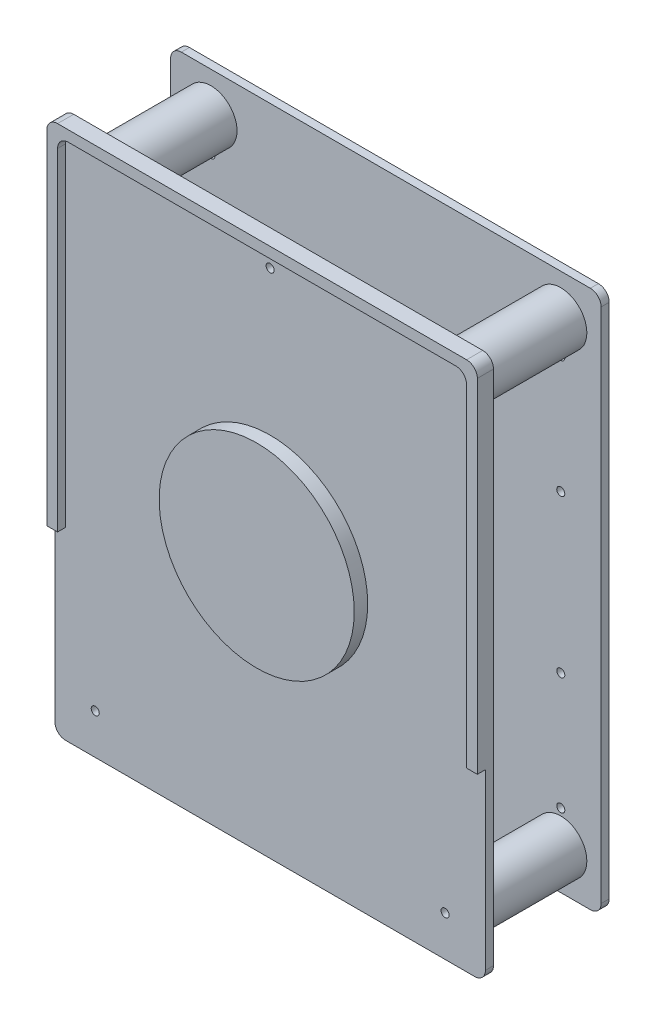
SolidWorks part; units mm, degrees
ref_plane "Front Plane" through (0, 0, 0) normal (0, 0, 1) x (1, 0, 0)
ref_plane "Top Plane" through (0, 0, 0) normal (0, 1, 0) x (1, 0, 0)
ref_plane "Right Plane" through (0, 0, 0) normal (1, 0, 0) x (0, 0, -1)
sketch "Sketch1" plane through (0, 0, 0) normal (0, 0, 1) x (1, 0, 0)
  line L0 (80, 0) -> (80, 200) construction
  line L1 (4, 0) -> (156, 0)
  line L2 (0, 4) -> (0, 196)
  line L3 (4, 200) -> (156, 200)
  line L4 (160, 4) -> (160, 196)
  line L5 (0, 100) -> (160, 100) construction
  arc A0 (4, 0) -> (0, 4) centre (4, 4) cw
  arc A1 (156, 0) -> (160, 4) centre (156, 4) ccw
  arc A2 (156, 200) -> (160, 196) centre (156, 196) cw
  arc A3 (0, 196) -> (4, 200) centre (4, 196) cw
  circle A4 centre (15, 15) radius 1.495
  circle A5 centre (145, 15) radius 1.495
  circle A6 centre (80, 190) radius 1.495
  circle A7 centre (80, 100) radius 36.25
  circle A8 centre (15, 15) radius 9.6889
  circle A9 centre (145, 15) radius 9.6889
  circle A10 centre (145, 185) radius 9.6889
  circle A11 centre (15, 185) radius 9.6889
  point P7 (0, 0)
  point P12 (160, 200)
  point P15 (0, 200)
  dimension "D3" = 4
  dimension "D4" = 15
  dimension "D5" = 10
  dimension "D6" = 15
  dimension "D1" = 200
  dimension "D2" = 160
extrude "Boss-Extrude1" add sketch "Sketch1" along normal blind 3 contours A3 L2 A0 L1 A1 L4 A2 L3 A9 A8 A7 A6 A10 A11 | A11 | A10 | A8 | A9 region at (2.9826, 2.9826, 0)
extrude "Cut-Extrude2" cut sketch "Sketch1<3>" along normal blind 3 contours A4
sketch "Sketch1<3>" plane through (0, 0, 0) normal (0, 0, 1) x (1, 0, 0) same geometry as "Sketch1"
extrude "Cut-Extrude3" cut sketch "Sketch1<4>" along normal blind 3 contours A5
sketch "Sketch1<4>" plane through (0, 0, 0) normal (0, 0, 1) x (1, 0, 0) same geometry as "Sketch1"
extrude "Boss-Extrude2" add sketch "Sketch1<6>" against normal blind 40 contours A10
sketch "Sketch1<6>" plane through (0, 0, 0) normal (0, 0, 1) x (1, 0, 0) same geometry as "Sketch1"
extrude "Boss-Extrude3" add sketch "Sketch1<7>" against normal blind 40 contours A9 A5 | A8 A4 | A11 region at (5.5851, 15, 0) region at (135.5851, 15, 0)
sketch "Sketch1<7>" plane through (0, 0, 0) normal (0, 0, 1) x (1, 0, 0) same geometry as "Sketch1"
sketch "Sketch2" plane through (0, 0, -40) normal (0, 0, -1) x (-1, 0, 0)
  line L1 (-156, 200) -> (-4, 200)
  line L2 (-160, 196) -> (-160, 4)
  line L3 (-156, 0) -> (-4, 0)
  line L4 (0, 196) -> (0, 4)
  arc A0 (-160, 4) -> (-156, 0) centre (-156, 4) ccw
  arc A1 (-4, 0) -> (0, 4) centre (-4, 4) ccw
  arc A2 (-4, 200) -> (0, 196) centre (-4, 196) cw
  arc A3 (-156, 200) -> (-160, 196) centre (-156, 196) ccw
  point P10 (0, 0)
  point P15 (-160, 200)
  dimension "D1" = 4
extrude "Boss-Extrude4" add sketch "Sketch2" along normal blind 3
extrude "Boss-Extrude5" add sketch "Sketch1<8>" along normal blind 8 contours A7
sketch "Sketch1<8>" plane through (0, 0, 0) normal (0, 0, 1) x (1, 0, 0) same geometry as "Sketch1"
sketch "Sketch3" plane through (0, 0, 3) normal (0, 0, 1) x (1, 0, 0)
  line L0 (0, 68.5733) -> (0, 196)
  line L1 (0, 4) -> (0, 196) construction
  line L2 (4, 200) -> (156, 200)
  line L3 (160, 196) -> (160, 68.5733)
  line L4 (160, 4) -> (160, 196) construction
  line L5 (0, 68.5733) -> (4, 68.5733)
  line L6 (4, 68.5733) -> (4, 192)
  line L7 (8, 196) -> (152, 196)
  line L8 (156, 192) -> (156, 68.5733)
  line L9 (156, 68.5733) -> (160, 68.5733)
  arc A0 (156, 200) -> (160, 196) centre (156, 196) cw
  arc A1 (152, 196) -> (156, 192) centre (152, 192) cw
  arc A2 (4, 192) -> (8, 196) centre (8, 192) cw
  arc A3 (0, 196) -> (4, 200) centre (4, 196) cw
  point P18 (160, 200)
  point P21 (156, 196)
  point P24 (4, 196)
  point P27 (0, 200)
  dimension "D1" = 4
extrude "Boss-Extrude6" add sketch "Sketch3" along normal blind 3
sketch "Sketch4" plane through (0, 0, -40) normal (0, 0, 1) x (1, 0, 0)
  line L0 (0, 170) -> (160, 170) construction
  line L1 (0, 4) -> (0, 196) construction
  line L2 (160, 4) -> (160, 196) construction
  line L3 (0, 132) -> (160, 132) construction
  line L4 (0, 30) -> (160, 30) construction
  line L5 (0, 68) -> (160, 68) construction
  line L6 (15, 15) -> (15, 185) construction
  line L7 (145, 185) -> (145, 15) construction
  line L8 (80, 0) -> (80, 200) construction
  line L9 (160, 100) -> (0, 100) construction
  circle A0 centre (15, 185) radius 9.6889 construction
  circle A1 centre (15, 15) radius 9.6889 construction
  circle A2 centre (15, 27.2478) radius 1.495
  circle A3 centre (145, 27.2478) radius 1.495
  circle A4 centre (145, 172.7522) radius 1.495
  circle A5 centre (15, 172.7522) radius 1.495
  circle A6 centre (15, 129.0797) radius 1.495
  circle A7 centre (15, 70.7167) radius 1.495
  circle A8 centre (145, 70.7167) radius 1.495
  circle A9 centre (145, 129.0797) radius 1.495
  dimension "D3" = 15
  dimension "D1" = 38
  dimension "D2" = 38
  dimension "D4" = 15
extrude "Cut-Extrude4" cut sketch "Sketch4" against normal blind 3 contours A5 | A4 | A2 | A3 | A6 | A7 | A8 | A9
